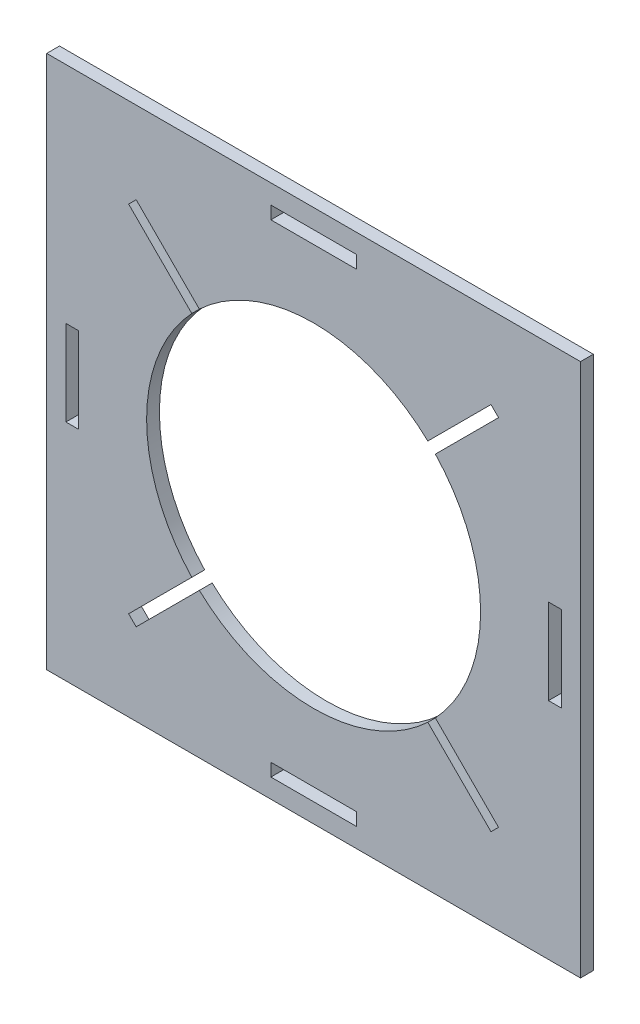
SolidWorks part; units mm, degrees
material "Pine"
ref_plane "Front Plane" through (0, 0, 0) normal (0, 0, 1) x (1, 0, 0)
ref_plane "Top Plane" through (0, 0, 0) normal (0, 1, 0) x (1, 0, 0)
ref_plane "Right Plane" through (0, 0, 0) normal (1, 0, 0) x (0, 0, -1)
sketch "Sketch1" plane through (0, 0, 0) normal (0, 0, 1) x (1, 0, 0)
  line L1 (-125, -125) -> (125, -125)
  line L2 (-125, -125) -> (-125, 125)
  line L3 (-125, 125) -> (125, 125)
  line L4 (125, -125) -> (125, 125)
  point P5 (0, 125)
  point P6 (125, 0)
  dimension "D1" = 250
extrude "Boss-Extrude1" add sketch "Sketch1" along normal blind 6
sketch "Sketch2" plane through (0, 0, 6) normal (0, 0, 1) x (1, 0, 0)
  line L0 (125, 125) -> (-125, 125) construction
  line L1 (-125, 125) -> (-125, -125) construction
  circle A0 centre (0, 0) radius 78.2
  point P5 (0, 125)
  point P8 (-125, 0)
  dimension "D1" = 156.4
extrude "Cut-Extrude1" cut sketch "Sketch2" against normal through all
sketch "Sketch3" plane through (0, 0, 6) normal (0, 0, 1) x (1, 0, 0)
  line L0 (0, 0) -> (-84.8528, 84.8528) construction
  line L1 (0, 0) -> (0, 78.2) construction
  line L2 (-57.0353, 53.4997) -> (-86.6206, 83.085)
  line L3 (-86.6206, 83.085) -> (-83.085, 86.6206)
  line L4 (-83.085, 86.6206) -> (-53.4997, 57.0353)
  circle A0 centre (0, 0) radius 78.2 construction
  arc A1 (-53.4997, 57.0353) -> (-57.0353, 53.4997) centre (0, 0) ccw
  dimension "D1" = 45
  dimension "D2" = 120
  dimension "D3" = 5
extrude "Cut-Extrude2" cut sketch "Sketch3" against normal through all
ref_axis "Axis1" through (0, 0, -0.3) along (0, 0, 1)
pattern_circular "CirPattern1" count 4 over 360 about axis through (0, 0, -0.3) along (0, 0, 1) of "Cut-Extrude2"
sketch "Sketch4" plane through (0, 0, 6) normal (0, 0, 1) x (1, 0, 0)
  line L1 (-20, 116) -> (20, 116)
  line L2 (-20, 116) -> (-20, 110)
  line L3 (-20, 110) -> (20, 110)
  line L4 (20, 116) -> (20, 110)
  point P4 (0, 110)
  dimension "D1" = 6
  dimension "D2" = 40
  dimension "D3" = 110
extrude "Cut-Extrude3" cut sketch "Sketch4" against normal through all contours L1 L4 L3 L2
pattern_circular "CirPattern2" count 4 over 360 about axis through (0, 0, -0.3) along (0, 0, 1) of "Cut-Extrude3"
